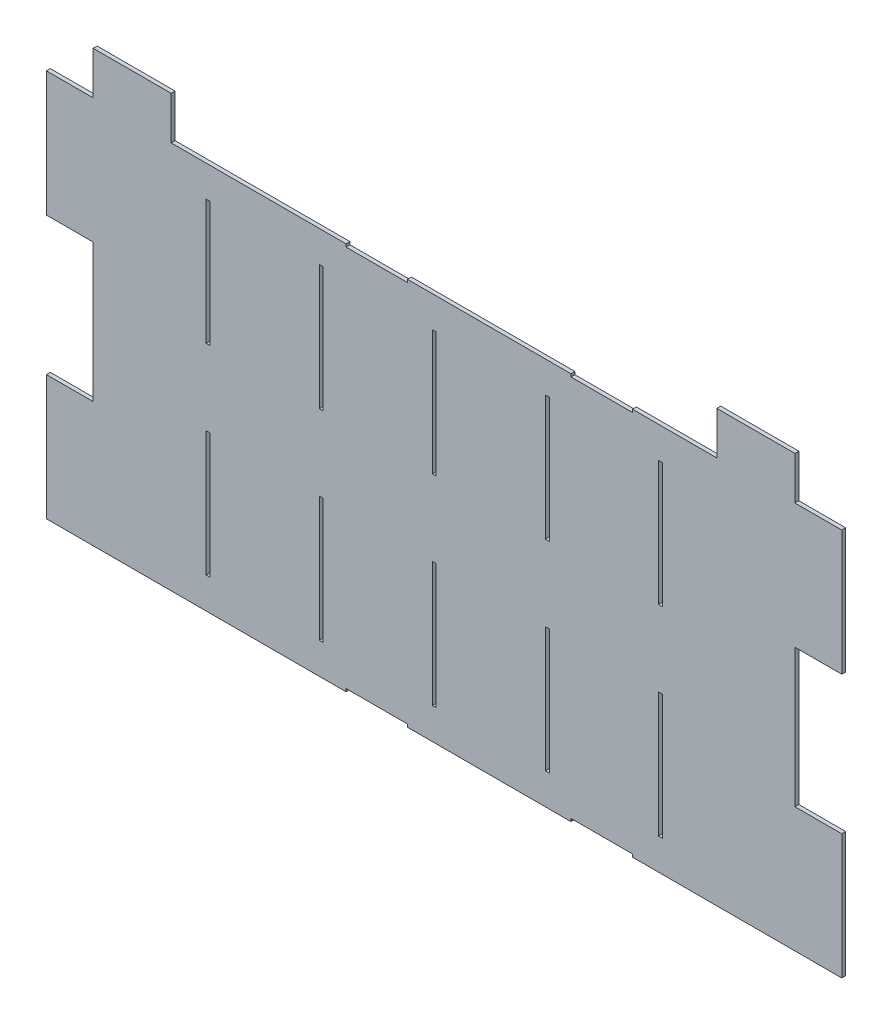
SolidWorks part; units mm, degrees
material "Custom Plastic"
ref_plane "X-Y Datum" through (0, 0, 0) normal (0, 0, 1) x (1, 0, 0)
ref_plane "X-Z Datum" through (0, 0, 0) normal (0, 1, 0) x (1, 0, 0)
ref_plane "Y-Z Datum" through (0, 0, 0) normal (1, 0, 0) x (0, 0, -1)
sketch "Sketch1" plane through (0, 0, 0) normal (0, 0, 1) x (1, 0, 0)
  line L0 (-285.4305, 0) -> (285.4305, 0) construction
  line L1 (-285.4305, -157.7875) -> (285.4305, -157.7875)
  line L2 (-285.4305, -157.7875) -> (-285.4305, 157.7875)
  line L3 (-285.4305, 157.7875) -> (285.4305, 157.7875)
  line L4 (285.4305, -157.7875) -> (285.4305, 157.7875)
  line L5 (-285.4305, -157.7875) -> (285.4305, 157.7875) construction
  line L6 (-285.4305, 157.7875) -> (285.4305, -157.7875) construction
  line L7 (-282.2555, -154.615) -> (-282.2555, 154.615)
  line L8 (-280.6655, -153.025) -> (-195.0655, -153.025)
  line L9 (-280.6655, -153.025) -> (-280.6655, 153.025)
  line L10 (-280.6655, 153.025) -> (-195.0655, 153.025)
  line L11 (-195.0655, -153.025) -> (-195.0655, 153.025)
  line L12 (-280.6655, -153.025) -> (-195.0655, 153.025) construction
  line L13 (-280.6655, 153.025) -> (-195.0655, -153.025) construction
  line L14 (-282.2555, 154.615) -> (-193.4755, 154.615)
  line L15 (-193.4755, -154.615) -> (-193.4755, 154.615)
  line L16 (-282.2555, -154.615) -> (-193.4755, -154.615)
  line L17 (-190.3005, 154.615) -> (-101.5205, 154.615)
  line L18 (-188.7105, 153.025) -> (-103.1105, 153.025)
  line L19 (-190.3005, -154.615) -> (-190.3005, 154.615)
  line L20 (-188.7105, -153.025) -> (-188.7105, 153.025)
  line L21 (-101.5205, -154.615) -> (-101.5205, 154.615)
  line L22 (-103.1105, -153.025) -> (-103.1105, 153.025)
  line L23 (-188.7105, -153.025) -> (-103.1105, -153.025)
  line L24 (-190.3005, -154.615) -> (-101.5205, -154.615)
  line L25 (-188.7105, -153.025) -> (-103.1105, 153.025) construction
  line L26 (-188.7105, 153.025) -> (-103.1105, -153.025) construction
  line L27 (-98.3455, 154.615) -> (-9.5655, 154.615)
  line L28 (-96.7555, 153.025) -> (-11.1555, 153.025)
  line L29 (-98.3455, -154.615) -> (-98.3455, 154.615)
  line L30 (-96.7555, -153.025) -> (-96.7555, 153.025)
  line L31 (-9.5655, -154.615) -> (-9.5655, 154.615)
  line L32 (-11.1555, -153.025) -> (-11.1555, 153.025)
  line L33 (-96.7555, -153.025) -> (-11.1555, -153.025)
  line L34 (-98.3455, -154.615) -> (-9.5655, -154.615)
  line L35 (-96.7555, -153.025) -> (-11.1555, 153.025) construction
  line L36 (-96.7555, 153.025) -> (-11.1555, -153.025) construction
  line L37 (-6.3905, 154.615) -> (82.3895, 154.615)
  line L38 (-4.8005, 153.025) -> (80.7995, 153.025)
  line L39 (-6.3905, -154.615) -> (-6.3905, 154.615)
  line L40 (-4.8005, -153.025) -> (-4.8005, 153.025)
  line L41 (82.3895, -154.615) -> (82.3895, 154.615)
  line L42 (80.7995, -153.025) -> (80.7995, 153.025)
  line L43 (-4.8005, -153.025) -> (80.7995, -153.025)
  line L44 (-6.3905, -154.615) -> (82.3895, -154.615)
  line L45 (-4.8005, -153.025) -> (80.7995, 153.025) construction
  line L46 (-4.8005, 153.025) -> (80.7995, -153.025) construction
  line L47 (85.5645, 154.615) -> (174.3445, 154.615)
  line L48 (87.1545, 153.025) -> (172.7545, 153.025)
  line L49 (85.5645, -154.615) -> (85.5645, 154.615)
  line L50 (87.1545, -153.025) -> (87.1545, 153.025)
  line L51 (174.3445, -154.615) -> (174.3445, 154.615)
  line L52 (172.7545, -153.025) -> (172.7545, 153.025)
  line L53 (87.1545, -153.025) -> (172.7545, -153.025)
  line L54 (85.5645, -154.615) -> (174.3445, -154.615)
  line L55 (87.1545, -153.025) -> (172.7545, 153.025) construction
  line L56 (87.1545, 153.025) -> (172.7545, -153.025) construction
  point P0 (0, 0)
  point P8 (-237.8655, 0)
  dimension "D1" = 570.861
  dimension "D2" = 315.575
  dimension "D3" = 306.05
  dimension "D4" = 85.6
  dimension "D5" = 3.175
  dimension "D8" = 3.175
  dimension "D6" = 1.59
  dimension "D7" = 5
extrude "Boss-Extrude1" add sketch "Sketch1" along normal blind 3.175 contours L8 L11 L10 L9 | L20 L23 L22 L18 | L30 L33 L32 L28 | L50 L53 L52 L48 | L49 L54 L51 L47 L53 L50 L48 L52 | L1 L4 L3 L2 L54 L49 L47 L51 L44 L39 L37 L41 L34 L29 L27 L31 L24 L19 L17 L21 L16 L7 L14 L15 | L40 L43 L42 L38 | L7 L16 L15 L14 L11 L8 L9 L10 | L19 L24 L21 L17 L23 L20 L18 L22 | L29 L34 L31 L27 L33 L30 L28 L32 | L39 L44 L41 L37 L43 L40 L38 L42 region at (-284.7782, 0, 0) region at (-281.9338, 0, 0) region at (-237.8655, 0, 0) region at (-145.9105, 154.2933, 0) region at (-145.9105, 0, 0) region at (-53.9555, 154.2933, 0) region at (-53.9555, 0, 0) region at (37.9995, 154.2933, 0) region at (37.9995, 0, 0) region at (129.9545, 154.2933, 0) region at (129.9545, 0, 0)
sketch "Sketch2" plane through (0, 0, 3.175) normal (0, 0, 1) x (1, 0, 0)
  line L0 (-190.3005, -154.615) -> (-193.4755, -154.615) construction
  line L1 (-191.888, -154.615) -> (-191.888, 157.7875) construction
  line L2 (-285.4305, 157.7875) -> (285.4305, 157.7875) construction
  line L4 (-193.4755, -30.7875) -> (-190.3005, -30.7875)
  line L5 (-193.4755, -30.7875) -> (-193.4755, -132.3875)
  line L6 (-193.4755, -132.3875) -> (-190.3005, -132.3875)
  line L7 (-190.3005, -30.7875) -> (-190.3005, -132.3875)
  line L8 (-193.4755, -30.7875) -> (-190.3005, -132.3875) construction
  line L9 (-193.4755, -132.3875) -> (-190.3005, -30.7875) construction
  line L12 (-285.4305, -157.7875) -> (285.4305, -157.7875) construction
  point P8 (-191.888, -81.5875)
  dimension "D1" = 76.2
  dimension "D2" = 3.175
  dimension "D3" = 101.6
extrude "Cut-Extrude1" cut sketch "Sketch2" against normal blind 3.175
sketch "Sketch7" plane through (0, 0, 3.175) normal (0, 0, 1) x (1, 0, 0)
  line L1 (103.2695, -155.5015) -> (153.2695, -155.5015)
  line L2 (103.2695, -155.5015) -> (103.2695, -157.7875)
  line L3 (103.2695, -157.7875) -> (153.2695, -157.7875)
  line L4 (153.2695, -155.5015) -> (153.2695, -157.7875)
  line L5 (-79.7305, -155.5015) -> (-29.7305, -155.5015)
  line L6 (-79.7305, -155.5015) -> (-79.7305, -157.7875)
  line L7 (-79.7305, -157.7875) -> (-29.7305, -157.7875)
  line L8 (-29.7305, -155.5015) -> (-29.7305, -157.7875)
extrude "Cut-Extrude5" cut sketch "Sketch7" against normal blind 3.175
mirror "Mirror3" about plane through (0, 0, 0) normal (0, 1, 0) of "Cut-Extrude1"
pattern_linear "LPattern2" count 5 spacing 91.96 along (1, 0, 0) of "Mirror3"
sketch "Sketch9" plane through (0, 0, 0) normal (0, 0, -1) x (-1, 0, 0)
  line L0 (-304.4805, -56.1875) -> (-304.4805, -157.7875) construction
  line L9 (-285.4305, 157.7875) -> (-221.9305, 157.7875)
  line L10 (-285.4305, 157.7875) -> (-285.4305, 192.7125)
  line L11 (-285.4305, 192.7125) -> (-221.9305, 192.7125)
  line L12 (-221.9305, 157.7875) -> (-221.9305, 192.7125)
  line L13 (-285.4305, 157.7875) -> (-323.5305, 157.7875)
  line L14 (-285.4305, 157.7875) -> (-285.4305, 56.1875)
  line L15 (-285.4305, 56.1875) -> (-323.5305, 56.1875)
  line L16 (-323.5305, 157.7875) -> (-323.5305, 56.1875)
  line L17 (-323.5305, 106.9875) -> (-285.4305, 106.9875) construction
  line L18 (-304.4805, 157.7875) -> (-304.4805, 113.3375)
  line L19 (-304.4805, 113.3375) -> (-304.4805, 56.1875) construction
  line L20 (-285.4305, -157.7875) -> (-323.5305, -157.7875)
  line L21 (-285.4305, -157.7875) -> (-285.4305, -88.7618)
  line L25 (-285.4305, -88.7618) -> (-285.4305, -56.1875)
  line L26 (-285.4305, -56.1875) -> (-323.5305, -56.1875)
  line L28 (-323.5305, -56.1875) -> (-323.5305, -157.7875)
  line L29 (-323.5305, -106.9875) -> (-285.4305, -106.9875) construction
  line L30 (-304.4805, -56.1875) -> (-304.4805, -106.9875) construction
  line L31 (-304.4805, -106.9875) -> (-304.4805, -157.7875) construction
  line L32 (-304.4805, -56.1875) -> (-304.4805, -106.9875) construction
  line L33 (-304.4805, -106.9875) -> (-304.4805, -157.7875) construction
  circle A0 centre (-304.4805, 135.5625) radius 3 construction
  circle A1 centre (-304.4805, 84.7625) radius 3 construction
  circle A2 centre (-304.4805, -81.5875) radius 3 construction
  circle A3 centre (-304.4805, -132.3875) radius 3 construction
  dimension "D1" = 6
  dimension "D2" = 6
  dimension "D3" = 63.5
  dimension "D4" = 34.925
  dimension "D5" = 101.6
  dimension "D6" = 38.1
  dimension "D7" = 38.1
  dimension "D8" = 101.6
extrude "Boss-Extrude3" add sketch "Sketch9" against normal blind 3.175 contours L13 L16 L15 L14 | L9 L12 L11 L10 | L26 L28 L20 L21 L25 A3 A2 region at (253.6805, 175.25, 0) region at (304.4805, 106.9875, 0) region at (304.4805, -106.9875, 0)
mirror "Mirror4" about plane through (0, 0, 0) normal (1, 0, 0) of "Boss-Extrude3"
mirror "Mirror5" about plane through (0, 0, 0) normal (0, 1, 0) of "Cut-Extrude5"
